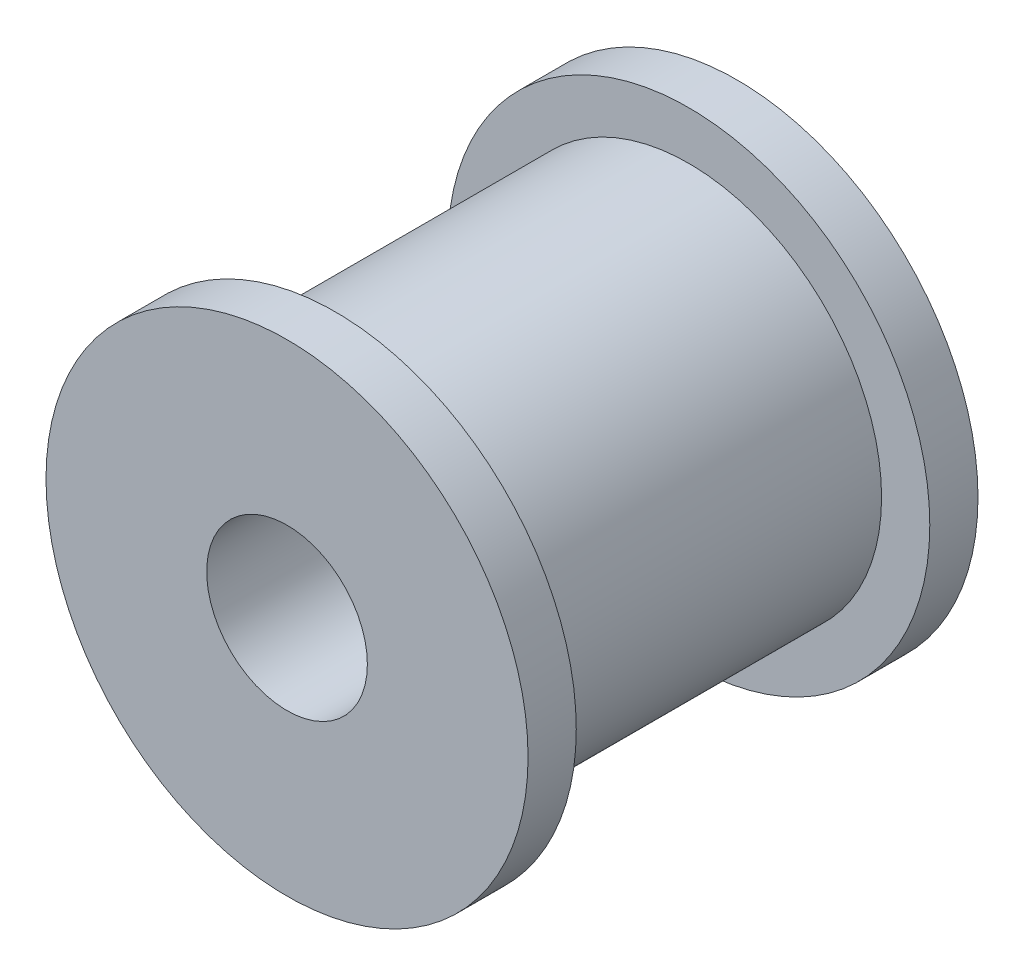
SolidWorks part; units mm, degrees
ref_plane "Alzado" through (0, 0, 0) normal (0, 0, 1) x (1, 0, 0)
ref_plane "Planta" through (0, 0, 0) normal (0, 1, 0) x (1, 0, 0)
ref_plane "Vista lateral" through (0, 0, 0) normal (1, 0, 0) x (0, 0, -1)
sketch "Croquis1" plane through (0, 0, 0) normal (0, 1, 0) x (1, 0, 0)
  line L0 (0, 0) -> (0, 14)
  line L1 (0, 14) -> (7.5, 14)
  line L2 (7.5, 14) -> (7.5, 12.5)
  line L3 (7.5, 12.5) -> (6, 12.5)
  line L4 (6, 12.5) -> (6, 1.5)
  line L5 (6, 1.5) -> (7.5, 1.5)
  line L6 (7.5, 1.5) -> (7.5, 0)
  line L7 (7.5, 0) -> (0, 0)
  dimension "D1" = 14
  dimension "D2" = 11
  dimension "D3" = 1.5
  dimension "D4" = 7.5
  dimension "D5" = 7.5
  dimension "D6" = 6
revolve "Revolución1" add sketch "Croquis1" angle 360 about L0
sketch "Croquis2" plane through (0, 0, 0) normal (0, 0, 1) x (1, 0, 0)
  circle A0 centre (0, 0) radius 2.5
  dimension "D1" = 5
extrude "Cortar-Extruir1" cut sketch "Croquis2" against normal up to surface (14 mm away) up to face at (7.5, 0, -14)
